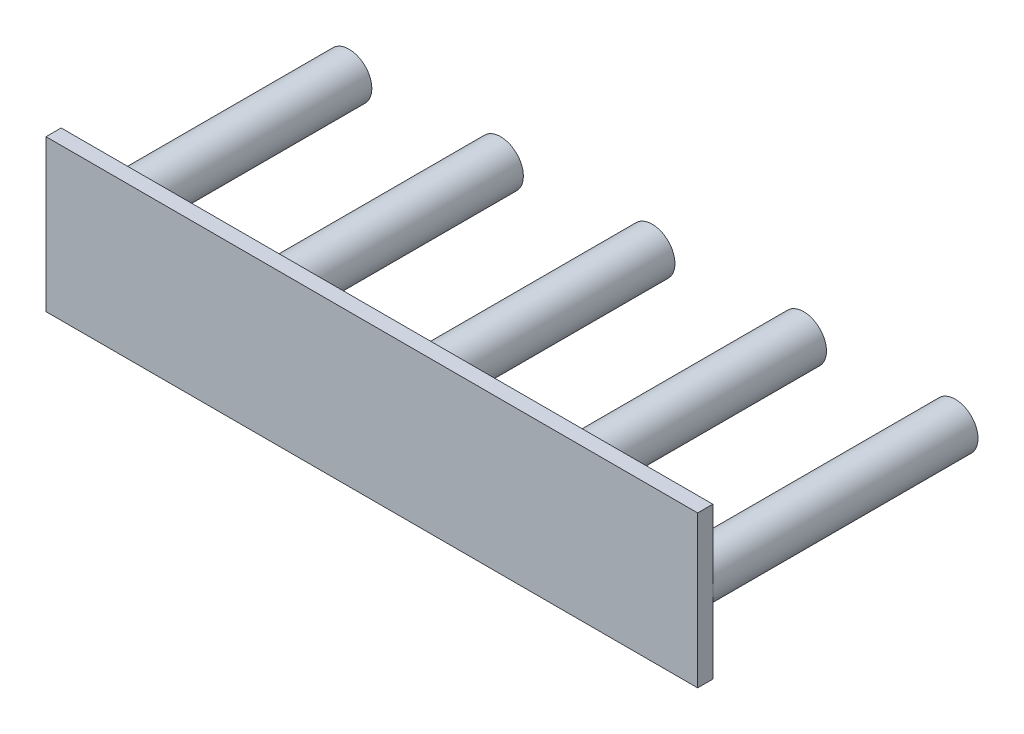
SolidWorks part; units mm, degrees
ref_plane "Front Plane" through (0, 0, 0) normal (0, 0, 1) x (1, 0, 0)
ref_plane "Top Plane" through (0, 0, 0) normal (0, 1, 0) x (1, 0, 0)
ref_plane "Right Plane" through (0, 0, 0) normal (1, 0, 0) x (0, 0, -1)
sketch "Esquisse1" plane through (0, 0, 0) normal (0, 0, 1) x (1, 0, 0)
  circle A0 centre (0, 0) radius 1.5
  circle A1 centre (0, 0) radius 3
  dimension "D1" = 6
  dimension "D2" = 3
extrude "Boss.-Extru.1" add sketch "Esquisse1" along normal blind 35
ref_axis "Axe1" through (3.3, 0, 0) along (-1, 0, 0)
pattern_linear "Répétition linéaire1" count 5 spacing 20 along (-1, 0, 0) of "Boss.-Extru.1"
sketch "Esquisse2" plane through (0, 0, 35) normal (0, 0, 1) x (1, 0, 0)
  line L1 (-83, 10) -> (3, 10)
  line L2 (-83, 10) -> (-83, -10)
  line L3 (-83, -10) -> (3, -10)
  line L4 (3, 10) -> (3, -10)
  line L5 (3.3, 0) -> (-3.3, 0) construction
  circle A1 centre (0, 0) radius 3 construction
  circle A2 centre (-80, 0) radius 3 construction
  point P4 (3, -4.9121)
  point P5 (0, 0)
  dimension "D1" = 20
  dimension "D2" = 10
extrude "Boss.-Extru.2" add sketch "Esquisse2" along normal blind 2
